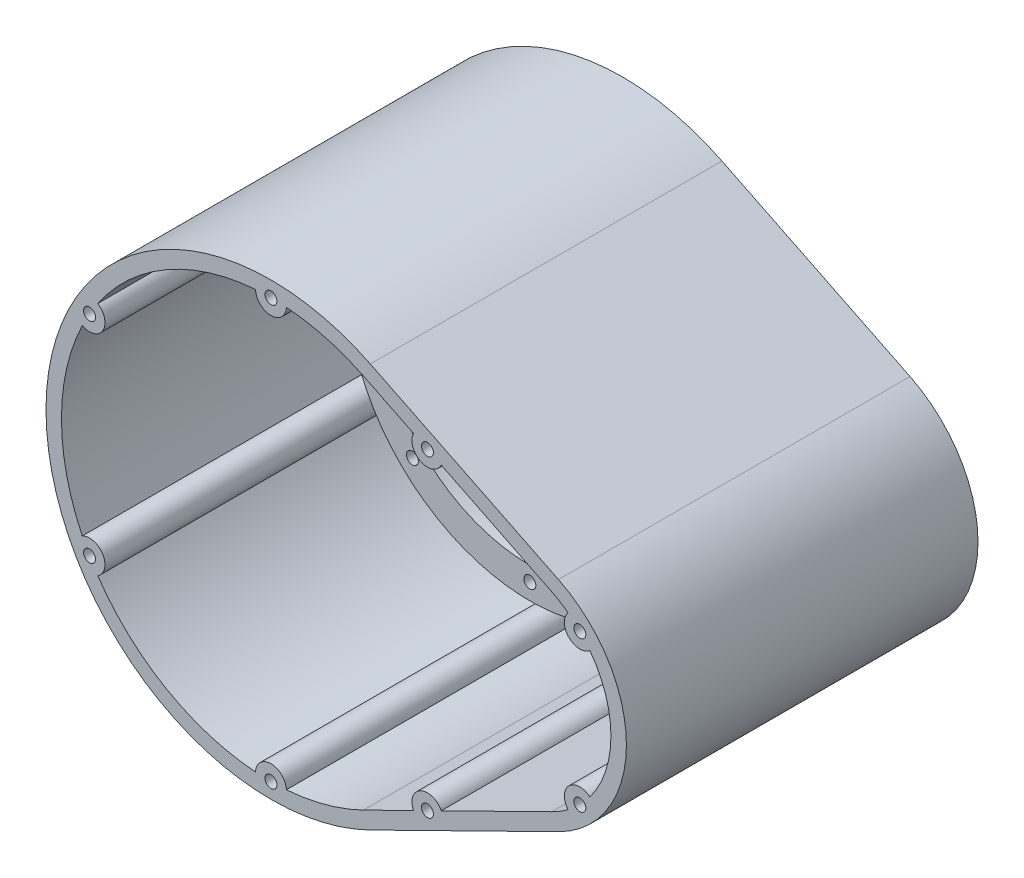
SolidWorks part; units mm, degrees
ref_plane "Front Plane" through (0, 0, 0) normal (0, 0, 1) x (1, 0, 0)
ref_plane "Top Plane" through (0, 0, 0) normal (0, 1, 0) x (1, 0, 0)
ref_plane "Right Plane" through (0, 0, 0) normal (1, 0, 0) x (0, 0, -1)
sketch "Sketch1" plane through (0, 0, 0) normal (0, 0, 1) x (1, 0, 0)
  line L0 (74.4125, 28.2611) -> (25.7142, 52.2345)
  line L1 (0, 0) -> (60.5, 0) construction
  line L5 (74.4125, -28.2611) -> (25.7142, -52.2345)
  circle A1 centre (0, 0) radius 58.2208 construction
  circle A11 centre (60.5, 0) radius 31.5 construction
  arc A12 (25.7142, 52.2345) -> (25.7142, -52.2345) centre (0, 0) ccw
  arc A13 (74.4125, 28.2611) -> (74.4125, -28.2611) centre (60.5, 0) cw
  point P22 (0, 0)
extrude "Boss-Extrude2" add sketch "Sketch1" along normal blind 8
sketch "Sketch5" plane through (0, 0, 8) normal (0, 0, 1) x (1, 0, 0)
  line L0 (20.8559, 42.3656) -> (69.5542, 18.3922)
  line L1 (69.5542, -18.3922) -> (20.8559, -42.3656)
  line L2 (17.3225, 35.1881) -> (66.0208, 11.2147)
  line L3 (17.3225, -35.1881) -> (66.0208, -11.2147)
  line L4 (0, 0) -> (60.5, 0) construction
  circle A0 centre (0, 0) radius 43.2208 construction
  circle A1 centre (60.5, 0) radius 16.5 construction
  circle A4 centre (60.5, 0) radius 12.5 construction
  circle A5 centre (60.5, 0) radius 20.5 construction
  circle A6 centre (0, 0) radius 39.2208 construction
  circle A7 centre (0, 0) radius 47.2208 construction
  arc A8 (20.8559, 42.3656) -> (20.8559, -42.3656) centre (0, 0) ccw
  arc A9 (17.3225, 35.1881) -> (17.3225, -35.1881) centre (0, 0) ccw
  arc A10 (66.0208, 11.2147) -> (66.0208, -11.2147) centre (60.5, 0) cw
  arc A11 (69.5542, 18.3922) -> (69.5542, -18.3922) centre (60.5, 0) cw
extrude "Boss-Extrude3" add sketch "Sketch5" along normal blind 16
sketch "Sketch6" plane through (0, 0, 24) normal (0, 0, 1) x (1, 0, 0)
  line L0 (0, 0) -> (0, 43) construction
  line L1 (60.5, 0) -> (77, 0) construction
  line L2 (20.8559, 42.3656) -> (69.5542, 18.3922) construction
  line L3 (20.8559, -42.3656) -> (69.5542, -18.3922) construction
  line L4 (20.8559, 42.3656) -> (34.716, 35.5424) construction
  line L5 (34.716, 35.5424) -> (32.9494, 31.9537) construction
  line L6 (69.5542, 18.3922) -> (60.5824, 22.8088) construction
  line L7 (60.5824, 22.8088) -> (58.8157, 19.2201) construction
  line L8 (20.8559, -42.3656) -> (34.716, -35.5424) construction
  line L9 (34.716, -35.5424) -> (32.9494, -31.9537) construction
  line L10 (69.5542, -18.3922) -> (60.5824, -22.8088) construction
  line L11 (60.5824, -22.8088) -> (58.8157, -19.2201) construction
  line L12 (0, 0) -> (60.5, 0) construction
  circle A0 centre (0, 43) radius 1.55
  circle A1 centre (60.5, 0) radius 16.5 construction
  circle A8 centre (77, 0) radius 1.55
  circle A9 centre (0, 0) radius 47.2208 construction
  circle A10 centre (60.5, 0) radius 20.5 construction
  arc A11 (69.5542, 18.3922) -> (69.5542, -18.3922) centre (60.5, 0) cw construction
  arc A12 (20.8559, 42.3656) -> (20.8559, -42.3656) centre (0, 0) ccw construction
  circle A13 centre (58.8157, 19.2201) radius 1.55
  circle A14 centre (32.9494, 31.9537) radius 1.55
  circle A15 centre (58.8157, -19.2201) radius 1.55
  circle A16 centre (32.9494, -31.9537) radius 1.55
  circle A17 centre (-30.4056, 30.4056) radius 1.55
  circle A18 centre (-43, 0) radius 1.55
  circle A19 centre (-30.4056, -30.4056) radius 1.55
  circle A20 centre (0, -43) radius 1.55
  point P21 (0.2659, 0.1121)
  point P41 (0, 0)
  dimension "D1" = 5
extrude "Cut-Extrude1" cut sketch "Sketch6" against normal up to surface (24 mm away) up to face at (33.4765, 0, 0)
sketch "Sketch7" plane through (0, 0, 8) normal (0, 0, 1) x (1, 0, 0)
  circle A0 centre (0, 0) radius 8.2
extrude "Cut-Extrude2" cut sketch "Sketch7" against normal blind 5 contours A0
sketch "Sketch8" plane through (0, 0, 8) normal (0, 0, 1) x (1, 0, 0)
  circle A0 centre (60.5, 0) radius 2
extrude "Boss-Extrude4" add sketch "Sketch8" along normal blind 8.5
sketch "Sketch9" plane through (0, 0, 0) normal (0, 0, -1) x (-1, 0, 0)
  line L0 (-77, 0) -> (0, 0) construction
  circle A10 centre (-77, 0) radius 3.5
  circle A11 centre (-58.8157, 19.2201) radius 3.5
  circle A12 centre (-32.9494, 31.9537) radius 3.5
  circle A13 centre (0, 43) radius 3.5
  circle A14 centre (30.4056, 30.4056) radius 3.5
  circle A15 centre (30.4056, -30.4056) radius 3.5
  circle A16 centre (0, -43) radius 3.5
  circle A17 centre (-32.9494, -31.9537) radius 3.5
  circle A18 centre (-58.8157, -19.2201) radius 3.5
  circle A19 centre (43, 0) radius 3.5
extrude "Cut-Extrude3" cut sketch "Sketch9" against normal blind 3
sketch "Sketch10" plane through (0, 0, 8) normal (0, 0, 1) x (1, 0, 0)
  line L1 (25.7142, 52.2345) -> (74.4125, 28.2611)
  line L3 (25.7142, -52.2345) -> (74.4125, -28.2611)
  line L6 (22.1809, 45.0571) -> (70.8792, 21.0837) construction
  line L7 (22.1809, -45.0571) -> (70.8792, -21.0837) construction
  line L8 (23.9475, 48.6458) -> (36.9095, 42.2649)
  line L9 (23.9475, -48.6458) -> (36.9095, -42.2649)
  line L10 (0, 0) -> (0, 54.2208) construction
  line L11 (0, 0) -> (40.4982, 40.4982) construction
  line L12 (60.5, 0) -> (79.9454, -19.4454) construction
  line L13 (60.5, 0) -> (79.9454, 19.4454) construction
  line L16 (0, 0) -> (58.5, 0) construction
  line L17 (0, 0) -> (40.4982, -40.4982) construction
  line L18 (44.0869, -38.7315) -> (72.6458, -24.6724)
  line L19 (44.0869, 38.7315) -> (72.6458, 24.6724)
  arc A33 (74.4125, 28.2611) -> (74.4125, -28.2611) centre (60.5, 0) cw
  arc A34 (25.7142, 52.2345) -> (25.7142, -52.2345) centre (0, 0) ccw
  arc A37 (70.8792, 21.0837) -> (70.8792, -21.0837) centre (60.5, 0) cw construction
  arc A38 (22.1809, 45.0571) -> (22.1809, -45.0571) centre (0, 0) ccw construction
  circle A47 centre (60.5, 0) radius 2 construction
  circle A48 centre (60.5, 0) radius 2 construction
  arc A51 (-48.8275, 23.5749) -> (-44.8302, 30.4984) centre (-46.9566, 27.1104) ccw
  arc A52 (-3.9973, 54.0733) -> (3.9973, 54.0733) centre (0, 54.2208) ccw
  arc A53 (36.9095, 42.2649) -> (44.0869, 38.7315) centre (40.4982, 40.4982) ccw
  arc A54 (76.9188, 22.0607) -> (82.5607, 16.4188) centre (79.9454, 19.4454) ccw
  arc A55 (76.9188, -22.0607) -> (82.5607, -16.4188) centre (79.9454, -19.4454) cw
  arc A56 (36.9095, -42.2649) -> (44.0869, -38.7315) centre (40.4982, -40.4982) cw
  arc A57 (-3.9973, -54.0733) -> (3.9973, -54.0733) centre (0, -54.2208) cw
  arc A58 (-48.8275, -23.5749) -> (-44.8302, -30.4984) centre (-46.9566, -27.1104) cw
  arc A59 (72.6458, 24.6724) -> (76.9188, 22.0607) centre (60.5, 0) cw
  arc A60 (23.9475, 48.6458) -> (3.9973, 54.0733) centre (0, 0) ccw
  arc A61 (-3.9973, 54.0733) -> (-44.8302, 30.4984) centre (0, 0) ccw
  arc A62 (-48.8275, 23.5749) -> (-48.8275, -23.5749) centre (0, 0) ccw
  arc A63 (3.9973, -54.0733) -> (23.9475, -48.6458) centre (0, 0) ccw
  arc A64 (-44.8302, -30.4984) -> (-3.9973, -54.0733) centre (0, 0) ccw
  arc A65 (76.9188, -22.0607) -> (72.6458, -24.6724) centre (60.5, 0) cw
  arc A66 (82.5607, 16.4188) -> (82.5607, -16.4188) centre (60.5, 0) cw
  point P28 (0, 0)
extrude "Boss-Extrude5" add sketch "Sketch10" along normal blind 83
sketch "Sketch11" plane through (0, 0, 91) normal (0, 0, 1) x (1, 0, 0)
  line L0 (0, 0) -> (60.5, 0) construction
  line L1 (23.9475, 48.6458) -> (72.6458, 24.6724) construction
  line L2 (23.9475, -48.6458) -> (72.6458, -24.6724) construction
  line L3 (44.0869, -38.7315) -> (72.6458, -24.6724) construction
  line L4 (0, 0) -> (40.4982, 40.4982) construction
  line L5 (60.5, 0) -> (79.9454, 19.4454) construction
  circle A15 centre (60.5, 0) radius 27.5 construction
  circle A16 centre (0, 0) radius 54.2208 construction
  circle A17 centre (0, 54.2208) radius 1.55
  circle A18 centre (-46.9566, 27.1104) radius 1.55
  circle A19 centre (-46.9566, -27.1104) radius 1.55
  circle A20 centre (0, -54.2208) radius 1.55
  circle A21 centre (79.9454, 19.4454) radius 1.55
  circle A23 centre (40.4982, 40.4982) radius 1.55
  circle A24 centre (79.9454, -19.4454) radius 1.55
  circle A25 centre (40.4982, -40.4982) radius 1.55
  point P22 (0, 0)
extrude "Cut-Extrude4" cut sketch "Sketch11" against normal blind 10 and the other way through all
